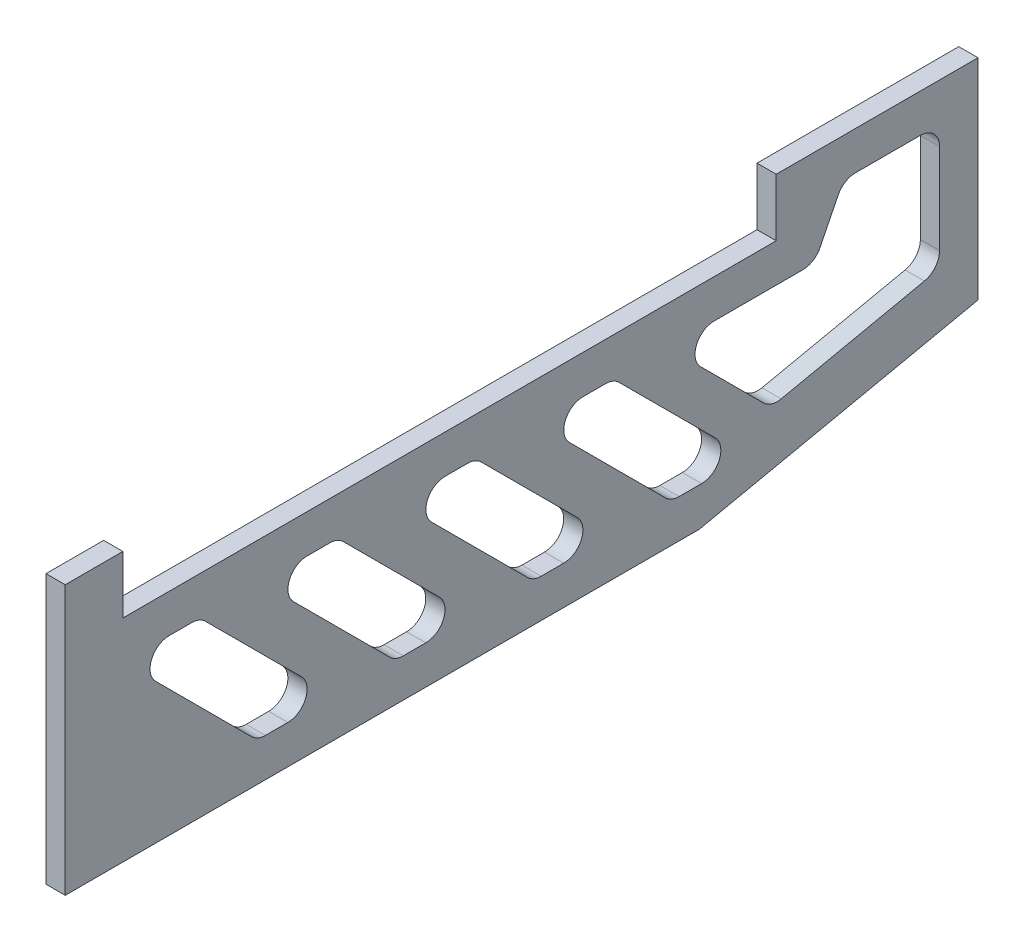
SolidWorks part; units mm, degrees
ref_plane "Ebene vorne" through (0, 0, 0) normal (0, 0, 1) x (1, 0, 0)
ref_plane "Ebene oben" through (0, 0, 0) normal (0, 1, 0) x (1, 0, 0)
ref_plane "Ebene rechts" through (0, 0, 0) normal (1, 0, 0) x (0, 0, -1)
sketch "Skizze1" plane through (0, 0, 0) normal (1, 0, 0) x (0, 0, -1)
  line L1 (0, 0) -> (237.5, 0)
  line L2 (0, 0) -> (0, 70)
  line L3 (0, 70) -> (237.5, 70)
  line L4 (237.5, 0) -> (237.5, 70)
  dimension "D1" = 70
  dimension "D2" = 237.5
extrude "Aufsatz-Linear austragen1" add sketch "Skizze1" along normal blind 5
sketch "Skizze2" plane through (5, 0, 0) normal (1, 0, 0) x (0, 0, -1)
  line L0 (165, 0) -> (237.5, 15.4104)
  line L1 (0, 0) -> (237.5, 0) construction
  line L2 (237.5, 0) -> (237.5, 70) construction
  line L3 (237.5, 15.4104) -> (237.5, 0)
  line L4 (237.5, 0) -> (165, 0)
  dimension "D1" = 12
  dimension "D2" = 165
extrude "Schnitt-Linear austragen1" cut sketch "Skizze2" against normal through all
sketch "Skizze3" plane through (5, 0, 0) normal (1, 0, 0) x (0, 0, -1)
  line L0 (237.5, 70) -> (0, 70) construction
  line L1 (15, 70) -> (185, 70)
  line L2 (15, 70) -> (15, 55)
  line L3 (15, 55) -> (185, 55)
  line L4 (185, 70) -> (185, 55)
  line L5 (0, 70) -> (0, 0) construction
  dimension "D1" = 170
  dimension "D2" = 15
  dimension "D3" = 15
extrude "Schnitt-Linear austragen2" cut sketch "Skizze3" against normal blind 5
sketch "Skizze4" plane through (5, 0, 0) normal (1, 0, 0) x (0, 0, -1)
  line L0 (15, 55) -> (15, 27.5) construction
  line L1 (15, 27.5) -> (15, 0) construction
  line L2 (0, 0) -> (165, 0) construction
  line L3 (15, 27.5) -> (237.5, 27.5) construction
  line L4 (237.5, 15.4104) -> (237.5, 70) construction
  line L5 (15, 45) -> (50, 10)
  line L6 (15, 45) -> (35, 45)
  line L7 (50, 10) -> (70, 10)
  line L8 (35, 45) -> (70, 10)
  line L9 (15, 55) -> (185, 55) construction
  line L10 (50.8845, 27.5) -> (273.3845, 27.5) construction
  line L11 (50.8845, 45) -> (70.8845, 45)
  line L12 (70.8845, 45) -> (105.8845, 10)
  line L13 (85.8845, 10) -> (105.8845, 10)
  line L14 (50.8845, 45) -> (85.8845, 10)
  line L15 (86.769, 27.5) -> (309.269, 27.5) construction
  line L16 (86.769, 45) -> (106.769, 45)
  line L17 (106.769, 45) -> (141.769, 10)
  line L18 (121.769, 10) -> (141.769, 10)
  line L19 (86.769, 45) -> (121.769, 10)
  line L20 (122.6535, 27.5) -> (345.1535, 27.5) construction
  line L21 (122.6535, 45) -> (142.6535, 45)
  line L22 (142.6535, 45) -> (177.6535, 10)
  line L23 (157.6535, 10) -> (177.6535, 10)
  line L24 (122.6535, 45) -> (157.6535, 10)
  line L25 (227.5, 60) -> (227.5, 27.5)
  line L26 (227.5, 27.5) -> (183.6222, 18.1735)
  line L27 (183.6222, 18.1735) -> (156.7957, 45)
  line L28 (156.7957, 45) -> (195, 45)
  line L29 (195, 45) -> (202.5, 60)
  line L30 (202.5, 60) -> (227.5, 60)
  line L32 (237.5, 15.4104) -> (165, 0) construction
  line L33 (237.5, 70) -> (185, 70) construction
  line L34 (185, 55) -> (185, 70) construction
  point P3 (32.5, 27.5)
  dimension "D1" = 10
  dimension "D2" = 45
  dimension "D3" = 20
  dimension "D5" = 10
  dimension "D6" = 10
  dimension "D7" = 10
  dimension "D8" = 10
  dimension "D9" = 25
  dimension "D10" = 10
  dimension "D4" = 4
extrude "Schnitt-Linear austragen3" cut sketch "Skizze4" against normal through all
fillet "Verrundung1" radius 5 22 edges at (2.5, 10, -157.6535) (2.5, 10, -177.6535) (2.5, 45, -142.6535) (2.5, 45, -122.6535) (2.5, 45, -86.769) (2.5, 45, -106.769) (2.5, 10, -141.769) (2.5, 10, -121.769) (2.5, 10, -85.8845) (2.5, 10, -105.8845) (2.5, 45, -70.8845) (2.5, 45, -50.8845) (2.5, 10, -50) (2.5, 10, -70) (2.5, 45, -35) (2.5, 45, -15) (2.5, 18.1735, -183.6222) (2.5, 27.5, -227.5) (2.5, 60, -227.5) (2.5, 45, -195) (2.5, 60, -202.5) (2.5, 45, -156.7957)
